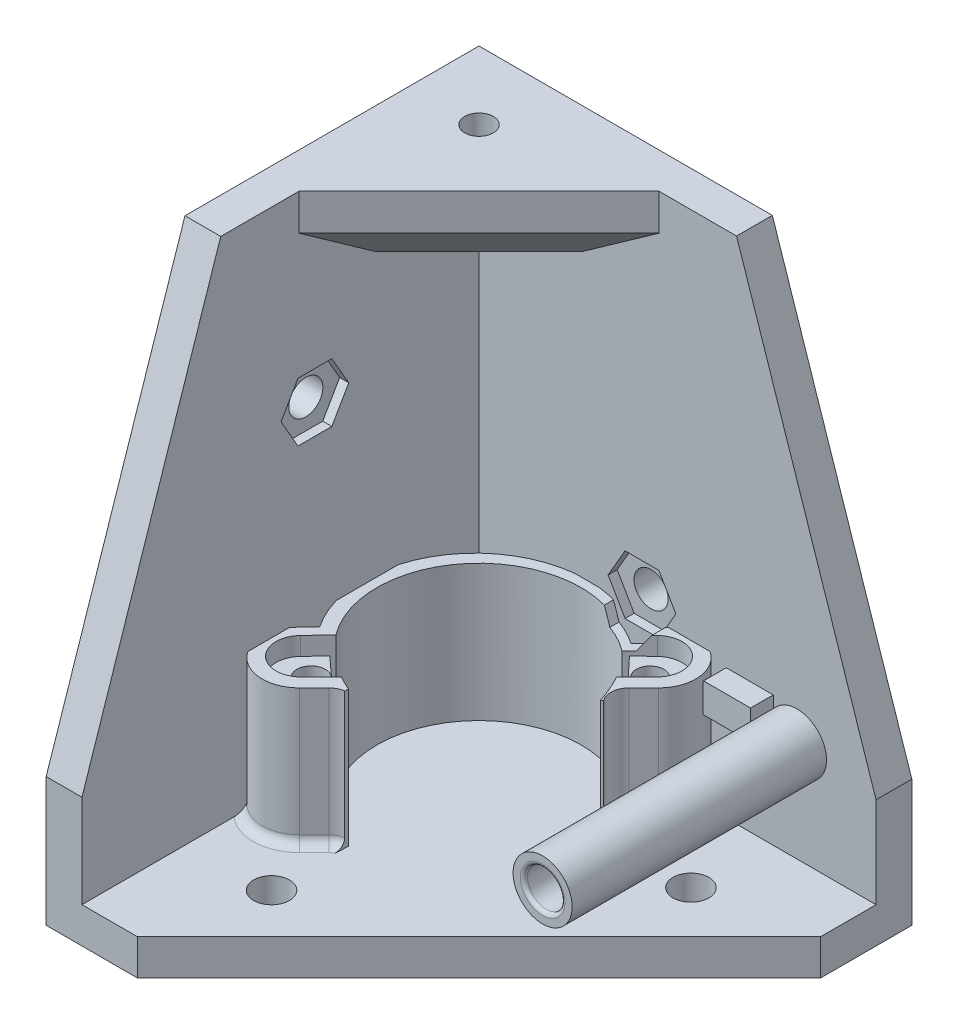
SolidWorks part; units mm, degrees
ref_plane "Front" through (0, 0, 0) normal (0, 0, 1) x (1, 0, 0)
ref_plane "Top" through (0, 0, 0) normal (0, 1, 0) x (1, 0, 0)
ref_plane "Right" through (0, 0, 0) normal (1, 0, 0) x (0, 0, -1)
sketch "Sketch1" plane through (0, 0, 0) normal (0, 1, 0) x (1, 0, 0)
  line L0 (0, 0) -> (0, 60.5)
  line L1 (0, -55) -> (0, 55) construction
  line L2 (0, 60.5) -> (60.5, 60.5)
  line L3 (60.5, 60.5) -> (60.5, 47.75)
  line L4 (60.5, 47.75) -> (12.75, 0)
  line L5 (-55, 0) -> (55, 0) construction
  line L6 (12.75, 0) -> (0, 0)
  dimension "D1" = 60.5
  dimension "D2" = 12.75
extrude "Boss-Extrude1" add sketch "Sketch1" along normal blind 5
sketch "Sketch4" plane through (0, 0, 0) normal (-1, 0, 0) x (0, 0, 1)
  line L0 (-60.5, 5) -> (-60.5, 76.1962)
  line L1 (-60.5, 76.1962) -> (-19.4, 76.1962)
  line L2 (-19.4, 76.1962) -> (0, 18.0048)
  line L3 (0, 18.0048) -> (0, 5)
  line L4 (0, -2.75) -> (0, 2.75) construction
  line L5 (-60.5, 5) -> (0, 5) construction
  line L6 (-60.5, 5) -> (0, 5)
  dimension "D1" = 71.1962
  dimension "D2" = 41.1
  dimension "D3" = 61.34
extrude "Boss-Extrude2" add sketch "Sketch4" against normal blind 5
sketch "Sketch5" plane through (0, 0, -60.5) normal (0, 0, -1) x (-1, 0, 0)
  line L0 (0, 76.1962) -> (-41, 76.1962)
  line L1 (-41, 76.1962) -> (-60.5, 17.7009)
  line L2 (-60.5, 17.7009) -> (-60.5, 5)
  line L6 (-60.5, 0) -> (0, 0)
  line L7 (0, 0) -> (0, 76.1962)
  line L8 (0, 76.1962) -> (-5, 76.1962)
  line L9 (-5, 76.1962) -> (-5, 5)
  line L10 (-5, 5) -> (-60.5, 5)
  line L11 (-60.5, 5) -> (-60.5, 0)
  line L12 (-60.5, 0) -> (0, 0)
  line L13 (0, 0) -> (0, 76.1962)
  line L14 (0, 76.1962) -> (-5, 76.1962)
  line L15 (-5, 76.1962) -> (-5, 5)
  line L16 (-5, 5) -> (-60.5, 5)
  line L17 (-60.5, 5) -> (-60.5, 0)
  line M13 (-5, 76.1962) -> (-5, 5)
  line M14 (-5, 5) -> (-60.5, 5)
  dimension "D2" = 41
  dimension "D3" = 61.66
  dimension "D1" = 0
extrude "Boss-Extrude3" add sketch "Sketch5" against normal blind 5 contours L1 L2 L0 M14 M13 region at (29.1655, 37.8824, -60.5)
sketch "Sketch6" plane through (0, 5, 0) normal (0, 1, 0) x (1, 0, 0)
  line L0 (60.5, 60.5) -> (0, 60.5) construction
  line L4 (0, 19.4) -> (0, 0)
  line L5 (60.5, 55.5) -> (5, 55.5)
  line L6 (5, 55.5) -> (5, 0)
  line L7 (5, 0) -> (12.75, 0)
  line L8 (12.75, 0) -> (60.5, 47.75)
  line L9 (60.5, 47.75) -> (60.5, 55.5)
  line L10 (60.5, 55.5) -> (5, 55.5)
  line L11 (5, 55.5) -> (5, 0)
  line L12 (5, 0) -> (12.75, 0)
  line L13 (12.75, 0) -> (60.5, 47.75)
  line L14 (60.5, 47.75) -> (60.5, 55.5)
  line L15 (0, 0) -> (5, 0)
  line L16 (5, 0) -> (5, 19.4)
  line L17 (5, 19.4) -> (0, 19.4)
  line L18 (0, 19.4) -> (0, 0)
  line L19 (0, 0) -> (5, 0)
  line L20 (5, 0) -> (5, 19.4)
  line L21 (5, 19.4) -> (0, 19.4)
  line L24 (0, 60.5) -> (0, 19.4)
  line L25 (0, 19.4) -> (5, 19.4)
  line L26 (5, 19.4) -> (5, 55.5)
  line L27 (5, 55.5) -> (41, 55.5)
  line L28 (41, 55.5) -> (41, 60.5)
  line L29 (41, 60.5) -> (0, 60.5)
  line L30 (0, 60.5) -> (0, 19.4)
  line L31 (0, 19.4) -> (5, 19.4)
  line L32 (5, 19.4) -> (5, 55.5)
  line L33 (5, 55.5) -> (41, 55.5)
  line L34 (41, 55.5) -> (41, 60.5)
  line L35 (41, 60.5) -> (0, 60.5)
  circle A0 centre (16.5, 15) radius 2.5
  circle A1 centre (45.5, 44.625) radius 2.5
  dimension "D1" = 5
  dimension "D2" = 5
  dimension "D3" = 0
  dimension "D4" = 15
  dimension "D6" = 16.5
  dimension "D7" = 15
  dimension "D9" = 15.875
  dimension "D5" = 0
  dimension "D8" = 0
extrude "Cut-Extrude1" cut sketch "Sketch6" against normal through all contours A0 | A1 region at (16.5, 5, -15) region at (45.5, 5, -44.625)
sketch "Sketch9" plane through (0, 0, -55.5) normal (0, 0, 1) x (1, 0, 0)
  line L1 (5, 76.1962) -> (5, 5) construction
  line L5 (0, 0) -> (60.5, 0)
  line L6 (0, 76.1962) -> (0, 0)
  line L7 (41, 76.1962) -> (0, 76.1962)
  line L8 (60.5, 17.7009) -> (41, 76.1962)
  line L9 (60.5, 0) -> (60.5, 17.7009)
  line L10 (0, 0) -> (60.5, 0)
  line L11 (0, 76.1962) -> (0, 0)
  line L12 (41, 76.1962) -> (0, 76.1962)
  line L13 (60.5, 17.7009) -> (41, 76.1962)
  line L14 (60.5, 0) -> (60.5, 17.7009)
  line L15 (49.45, 19.0462) -> (49.45, 3.6199) construction
  circle A0 centre (49.45, 19.0462) radius 4.1275
  circle A1 centre (49.45, 19.0462) radius 2.6035
  dimension "D2" = 5.207
  dimension "D3" = 1.524
  dimension "D4" = 57.15
  dimension "D5" = 44.45
  dimension "D1" = 0
extrude "Boss-Extrude5" add sketch "Sketch9" along normal blind 35.56 contours A1 A0 region at (45.4392, 19.0462, -55.5)
fillet "Fillet1" radius 0.508 1 edges at (52.0535, 19.0462, -19.94)
sketch "Sketch14" plane through (0, 5, 0) normal (0, 1, 0) x (1, 0, 0)
  line L0 (13.4627, 27.5396) -> (14.7681, 26.7924)
  line L1 (12.75, 0) -> (60.5, 47.75) construction
  line L2 (36.625, 23.875) -> (5, 55.5) construction
  line L3 (5, 55.5) -> (60.5, 55.5) construction
  line L4 (32.9604, 47.0373) -> (33.7076, 45.7319)
  line L5 (14.8281, 26.8523) -> (11.8274, 23.8516)
  line L6 (6.723, 28.8027) -> (9.1327, 31.3641)
  line L7 (33.6477, 45.6719) -> (36.6484, 48.6726)
  line L8 (31.6973, 53.777) -> (29.1359, 51.3673)
  line L9 (15.0744, 24.4582) -> (13.006, 22.3898)
  line L10 (5.6561, 29.7396) -> (7.0609, 31.1444)
  line L11 (36.0418, 45.4256) -> (38.1102, 47.494)
  line L12 (30.7604, 54.8439) -> (28.83, 52.9135)
  line L13 (18.1324, 24.8665) -> (30.5234, 17.7734)
  line L14 (35.6335, 42.3676) -> (42.7266, 29.9766)
  line L15 (31.7409, 18.9909) -> (18.852, 25.7543)
  line L16 (41.5091, 28.7591) -> (34.7457, 41.648)
  line L17 (16.5689, 25.6946) -> (16.5343, 25.1798)
  line L18 (34.7457, 41.648) -> (35.7996, 42.0774)
  circle A0 centre (20.5607, 39.9393) radius 14.2875
  arc A1 (11.8274, 23.8516) -> (6.723, 28.8027) centre (9.3129, 26.3661) cw
  arc A2 (36.6484, 48.6726) -> (31.6973, 53.777) centre (34.1339, 51.1871) ccw
  arc A3 (13.006, 22.3898) -> (5.6561, 29.7396) centre (9.3311, 26.0647) cw
  arc A4 (38.1102, 47.494) -> (30.7604, 54.8439) centre (34.4353, 51.1689) ccw
  arc A5 (7.0609, 31.1444) -> (28.83, 52.9135) centre (20.0709, 39.9035) cw
  arc A6 (36.0418, 45.4256) -> (35.6335, 42.3676) centre (37.8378, 43.6295) ccw
  arc A7 (15.0744, 24.4582) -> (18.1324, 24.8665) centre (16.8705, 22.6622) cw
  arc A9 (33.8602, 45.8844) -> (36.3595, 38.5726) centre (13.6025, 34.877) cw
  arc A10 (14.6156, 26.6398) -> (21.9274, 24.1405) centre (25.623, 46.8975) ccw
  point P40 (34.6689, 44.0527)
  point P43 (16.4473, 25.8311)
  line M13 (60.5, 55.5) -> (5, 55.5)
  line M14 (5, 55.5) -> (5, 0)
  line M16 (12.75, 0) -> (60.5, 47.75)
  dimension "D1" = 28.575
  dimension "D2" = 3.556
  dimension "D3" = 2.54
extrude "Boss-Extrude6" add sketch "Sketch14" along normal blind 19.05 contours L2 A0 L5 A1 L6 A5 L10 A3 L9 A7 L13 M16 M14 | L2 L14 A6 L11 A4 L12 A5 A0 L8 A2 L7 M16 M13 region at (7.691, 5, -30.3062) region at (10.0875, 5, -50.8829)
sketch "Sketch15" plane through (0, 76.1962, 0) normal (0, 1, 0) x (1, 0, 0)
  line L0 (5, 30.3375) -> (30.1625, 55.5)
  line L1 (0, -33.275) -> (0, 33.275) construction
  line L2 (41, 60.5) -> (0, 60.5) construction
  line L6 (0, 60.5) -> (0, 19.4)
  line L7 (0, 19.4) -> (5, 19.4)
  line L8 (5, 19.4) -> (5, 55.5)
  line L9 (5, 55.5) -> (41, 55.5)
  line L10 (41, 55.5) -> (41, 60.5)
  line L11 (41, 60.5) -> (0, 60.5)
  line L13 (0, 19.4) -> (5, 19.4)
  line L14 (5, 30.3375) -> (5, 55.5)
  line L15 (5, 55.5) -> (30.1625, 55.5)
  line L16 (41, 55.5) -> (41, 60.5)
  circle A0 centre (9.525, 50.975) radius 2
  line M11 (5, 19.4) -> (5, 55.5)
  line M12 (5, 55.5) -> (41, 55.5)
  dimension "D3" = 4
  dimension "D4" = 9.525
  dimension "D5" = 9.525
  dimension "D2" = 45
  dimension "D1" = 0
extrude "Boss-Extrude7" add sketch "Sketch15" against normal blind 12.7 contours L0 A0 M11 M12 region at (13.5472, 76.1962, -46.9528)
chamfer "Chamfer2" distance 7.62 angle 45 1 edges at (17.5813, 63.4962, -42.9187)
fillet "Fillet2" radius 1.27 7 edges at (39.6065, 5, -51.6871) (37.076, 5, -46.4598) (35.3202, 5, -43.9657) (8.8129, 5, -20.8935) (14.0402, 5, -23.424) (15.745, 5, -24.9392) (35.7165, 5, -42.2225)
sketch "Sketch16" plane through (0, 0, -55.5) normal (0, 0, 1) x (1, 0, 0)
  line L1 (46.1305, 23.2107) -> (38.2864, 23.2107)
  line L2 (46.1305, 23.2107) -> (46.1305, 19.0978)
  line L3 (46.1305, 19.0978) -> (38.2864, 19.0978)
  line L4 (38.2864, 23.2107) -> (38.2864, 19.0978)
extrude "Boss-Extrude8" add sketch "Sketch16" along normal blind 3.175
chamfer "Chamfer3" distance 1.27 angle 45 1 edges at (38.2864, 23.2107, -55.0794)
sketch "Sketch17" plane through (0, 5, 0) normal (0, 1, 0) x (1, 0, 0)
  line L0 (8.716, 30.9212) -> (14.047, 26.0712)
  line L1 (36.625, 23.875) -> (5, 55.5) construction
  line L2 (12.75, 0) -> (60.5, 47.75) construction
  line L3 (5, 55.5) -> (18.418, 55.5) construction
  line L4 (5, 55.5) -> (5, 44.2452) construction
  line L5 (29.6632, 51.8634) -> (34.5959, 46.6202)
  line L22 (37.3079, 55.5) -> (31.5627, 55.5)
  line L23 (30.7604, 54.8439) -> (28.83, 52.9135)
  line L24 (21.7238, 55.5) -> (18.418, 55.5)
  line L25 (5, 44.2452) -> (5, 35.5618)
  line L26 (7.0609, 31.1444) -> (5.6561, 29.7396)
  line L27 (5, 28.9373) -> (5, 23.1921)
  line L28 (13.006, 22.3898) -> (15.0744, 24.4582)
  line L29 (16.5343, 25.1798) -> (16.5689, 25.6946)
  line L30 (16.5343, 25.1798) -> (16.5689, 25.6946)
  line L31 (35.539, 41.9712) -> (35.7996, 42.0774)
  line L32 (35.539, 41.9712) -> (35.7996, 42.0774)
  line L33 (14.6156, 26.6398) -> (11.8274, 23.8516)
  line L34 (6.723, 28.8027) -> (9.1327, 31.3641)
  line L35 (29.1359, 51.3673) -> (31.6973, 53.777)
  line L36 (36.6484, 48.6726) -> (33.8602, 45.8844)
  line L40 (35.7996, 42.0774) -> (35.6335, 42.3676)
  line L41 (36.0418, 45.4256) -> (38.1102, 47.494)
  line L43 (37.3079, 55.5) -> (31.5627, 55.5)
  line L44 (30.7604, 54.8439) -> (28.83, 52.9135)
  line L45 (21.7238, 55.5) -> (18.418, 55.5)
  line L46 (5, 44.2452) -> (5, 35.5618)
  line L47 (7.0609, 31.1444) -> (5.6561, 29.7396)
  line L48 (5, 28.9373) -> (5, 23.1921)
  line L49 (13.006, 22.3898) -> (15.0744, 24.4582)
  line L54 (14.6156, 26.6398) -> (11.8274, 23.8516)
  line L55 (6.723, 28.8027) -> (9.1327, 31.3641)
  line L56 (29.1359, 51.3673) -> (31.6973, 53.777)
  line L57 (36.6484, 48.6726) -> (33.8602, 45.8844)
  line L61 (35.7996, 42.0774) -> (35.6335, 42.3676)
  line L62 (36.0418, 45.4256) -> (38.1102, 47.494)
  circle A1 centre (33.6908, 50.7324) radius 2.1828
  circle A2 centre (10.0204, 27.0078) radius 1.9844
  circle A3 centre (33.6908, 50.7324) radius 1.9288
  arc A15 (38.1102, 47.494) -> (37.3079, 55.5) centre (34.4353, 51.1689) ccw
  arc A17 (31.5627, 55.5) -> (30.7604, 54.8439) centre (34.4353, 51.1689) ccw
  arc A18 (28.83, 52.9135) -> (21.7238, 55.5) centre (20.0709, 39.9035) ccw
  arc A19 (18.418, 55.5) -> (5, 44.2452) centre (20.0709, 39.9035) ccw
  arc A20 (5, 35.5618) -> (7.0609, 31.1444) centre (20.0709, 39.9035) ccw
  arc A21 (5.6561, 29.7396) -> (5, 28.9373) centre (9.3311, 26.0647) ccw
  arc A22 (5, 23.1921) -> (13.006, 22.3898) centre (9.3311, 26.0647) ccw
  arc A23 (16.5343, 25.1798) -> (15.0744, 24.4582) centre (16.8705, 22.6622) ccw
  arc A24 (14.6156, 26.6398) -> (16.5689, 25.6946) centre (25.623, 46.8975) ccw
  arc A25 (6.723, 28.8027) -> (11.8274, 23.8516) centre (9.3129, 26.3661) ccw
  arc A26 (29.1359, 51.3673) -> (9.1327, 31.3641) centre (20.5607, 39.9393) ccw
  arc A27 (36.6484, 48.6726) -> (31.6973, 53.777) centre (34.1339, 51.1871) ccw
  arc A28 (35.539, 41.9712) -> (33.8602, 45.8844) centre (13.6025, 34.877) ccw
  arc A29 (36.0418, 45.4256) -> (35.6335, 42.3676) centre (37.8378, 43.6295) ccw
  arc A30 (38.1102, 47.494) -> (37.3079, 55.5) centre (34.4353, 51.1689) ccw
  arc A32 (31.5627, 55.5) -> (30.7604, 54.8439) centre (34.4353, 51.1689) ccw
  arc A33 (28.83, 52.9135) -> (21.7238, 55.5) centre (20.0709, 39.9035) ccw
  arc A34 (18.418, 55.5) -> (5, 44.2452) centre (20.0709, 39.9035) ccw
  arc A35 (5, 35.5618) -> (7.0609, 31.1444) centre (20.0709, 39.9035) ccw
  arc A36 (5.6561, 29.7396) -> (5, 28.9373) centre (9.3311, 26.0647) ccw
  arc A37 (5, 23.1921) -> (13.006, 22.3898) centre (9.3311, 26.0647) ccw
  arc A38 (16.5343, 25.1798) -> (15.0744, 24.4582) centre (16.8705, 22.6622) ccw
  arc A39 (14.6156, 26.6398) -> (16.5689, 25.6946) centre (25.623, 46.8975) ccw
  arc A40 (6.723, 28.8027) -> (11.8274, 23.8516) centre (9.3129, 26.3661) ccw
  arc A41 (29.1359, 51.3673) -> (9.1327, 31.3641) centre (20.5607, 39.9393) ccw
  arc A42 (36.6484, 48.6726) -> (31.6973, 53.777) centre (34.1339, 51.1871) ccw
  arc A43 (35.539, 41.9712) -> (33.8602, 45.8844) centre (13.6025, 34.877) ccw
  arc A44 (36.0418, 45.4256) -> (35.6335, 42.3676) centre (37.8378, 43.6295) ccw
  line M44 (33.8602, 45.8844) -> (36.6484, 48.6726)
  arc M45 (36.6484, 48.6726) -> (31.6973, 53.777) centre (34.1339, 51.1871) ccw
  line M46 (31.6973, 53.777) -> (29.1359, 51.3673)
  line M48 (9.1327, 31.3641) -> (6.723, 28.8027)
  arc M49 (6.723, 28.8027) -> (11.8274, 23.8516) centre (9.3129, 26.3661) ccw
  line M50 (11.8274, 23.8516) -> (14.6156, 26.6398)
  dimension "D2" = 3.9688
  dimension "D3" = 0.254
  dimension "D1" = 0
extrude "Boss-Extrude9" add sketch "Sketch17" along normal offset from surface (16.51 mm away) 2.54 contours L5 A1 M46 M44 M45 | L0 M48 M49 M50 | A1 L5 A3 region at (11.3737, 5, -28.4876) region at (30.7585, 5, -52.737) region at (33.0584, 5, -52.7569) up to face at (20.9693, 24.05, -39.9839)
sketch "Sketch18" plane through (0, 0, 0) normal (-1, 0, 0) x (0, 0, 1)
  line L0 (-60.5, 76.1962) -> (-60.5, 0) construction
  line L1 (33.275, 0) -> (-33.275, 0) construction
  circle A0 centre (-32.56, 49.53) radius 2.3813
  dimension "D1" = 27.94
  dimension "D2" = 49.53
  dimension "D3" = 4.7625
extrude "Cut-Extrude2" cut sketch "Sketch18" against normal up to next
sketch "Sketch19" plane through (0, 0, -60.5) normal (0, 0, -1) x (-1, 0, 0)
  line L0 (0, 33.275) -> (0, -33.275) construction
  line L1 (33.275, 0) -> (-33.275, 0) construction
  circle A0 centre (-27.7812, 26.1937) radius 2.3813
  dimension "D1" = 27.7812
  dimension "D2" = 26.1937
  dimension "D3" = 4.7625
extrude "Cut-Extrude3" cut sketch "Sketch19" against normal up to next
sketch "Sketch20" plane through (0, 0, -55.5) normal (0, 0, 1) x (1, 0, 0)
  line L1 (32.5155, 26.1938) -> (30.1484, 30.2938)
  line L2 (30.1484, 30.2938) -> (25.4141, 30.2938)
  line L3 (25.4141, 30.2938) -> (23.047, 26.1938)
  line L4 (23.047, 26.1938) -> (25.4141, 22.0938)
  line L5 (25.4141, 22.0938) -> (30.1484, 22.0938)
  line L6 (30.1484, 22.0938) -> (32.5155, 26.1938)
  circle A0 centre (27.7812, 26.1937) radius 2.3813 construction
  circle A1 centre (27.7812, 26.1937) radius 2.3813
  circle A2 centre (27.7812, 26.1937) radius 4.1 construction
  dimension "D1" = 8.2
extrude "Cut-Extrude4" cut sketch "Sketch20" against normal blind 1.27 and the other way up to vertex (4.1327 mm away) contours L1 L2 L3 L4 L5 L6 other way up to point (29.1359, 24.05, -51.3673)
sketch "Sketch21" plane through (5, 0, 0) normal (1, 0, 0) x (0, 0, -1)
  line L1 (34.9271, 53.63) -> (30.1929, 53.63)
  line L2 (30.1929, 53.63) -> (27.8257, 49.53)
  line L3 (27.8257, 49.53) -> (30.1929, 45.43)
  line L4 (30.1929, 45.43) -> (34.9271, 45.43)
  line L5 (34.9271, 45.43) -> (37.2943, 49.53)
  line L6 (37.2943, 49.53) -> (34.9271, 53.63)
  circle A0 centre (32.56, 49.53) radius 2.3813 construction
  circle A1 centre (32.56, 49.53) radius 2.3812
  circle A2 centre (32.56, 49.53) radius 4.1 construction
  dimension "D1" = 8.2
extrude "Cut-Extrude5" cut sketch "Sketch21" against normal blind 1.27 contours L1 L2 L3 L4 L5 L6
sketch "Sketch23" plane through (0, 0, 0) normal (0, 1, 0) x (1, 0, 0)
  line L1 (60.5, 60.5) -> (101.14, 60.5)
  line L2 (60.5, 60.5) -> (60.5, 24.94)
  line L3 (60.5, 24.94) -> (101.14, 24.94)
  line L4 (101.14, 60.5) -> (101.14, 24.94)
  dimension "D1" = 40.64
  dimension "D2" = 35.56
extrude "Boss-Extrude12" [suppressed] add sketch "Sketch23" along normal blind 5.08
sketch "Sketch24" [suppressed] plane through (0, 5.08, 0) normal (0, 1, 0) x (1, 0, 0)
  line L0 (101.14, 60.5) -> (60.5, 60.5) construction
  line L1 (60.5, 47.75) -> (60.5, 55.5) construction
  circle A0 centre (65.58, 55.42) radius 1.7145
  circle A1 centre (96.06, 55.42) radius 1.7145
  circle A2 centre (96.06, 29.258) radius 1.7145
  circle A3 centre (65.58, 29.258) radius 1.7145
  dimension "D1" = 3.429
  dimension "D2" = 26.162
  dimension "D3" = 30.48
  dimension "D4" = 5.08
  dimension "D5" = 5.08
extrude "Cut-Extrude6" [suppressed] cut sketch "Sketch24" against normal up to next
sketch "Sketch25" plane through (0, 63.4962, 0) normal (0, -1, 0) x (1, 0, 0)
  line L1 (13.5665, -50.975) -> (11.5457, -47.475)
  line L2 (11.5457, -47.475) -> (7.5043, -47.475)
  line L3 (7.5043, -47.475) -> (5.4835, -50.975)
  line L4 (5.4835, -50.975) -> (7.5043, -54.475)
  line L5 (7.5043, -54.475) -> (11.5457, -54.475)
  line L6 (11.5457, -54.475) -> (13.5665, -50.975)
  circle A0 centre (9.525, -50.975) radius 2 construction
  circle A1 centre (9.525, -50.975) radius 2
  circle A2 centre (9.525, -50.975) radius 3.5 construction
  dimension "D1" = 7
extrude "Cut-Extrude7" cut sketch "Sketch25" against normal blind 4
